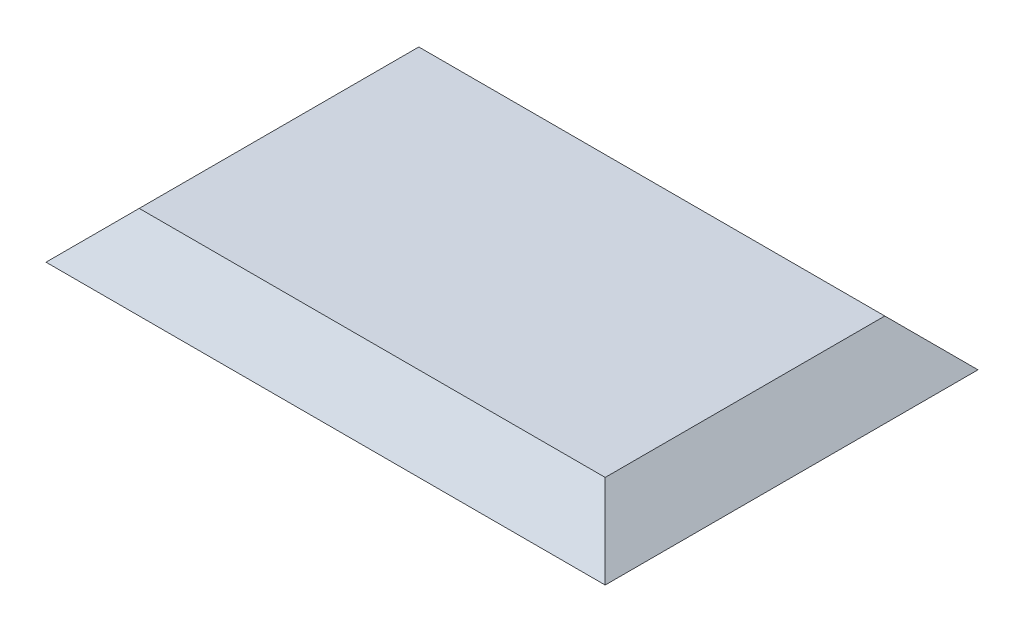
SolidWorks part; units mm, degrees
ref_plane "Plan de face" through (0, 0, 0) normal (0, 0, 1) x (1, 0, 0)
ref_plane "Plan de dessus" through (0, 0, 0) normal (0, 1, 0) x (1, 0, 0)
ref_plane "Plan de droite" through (0, 0, 0) normal (1, 0, 0) x (0, 0, -1)
sketch "Esquisse1" plane through (0, 0, 0) normal (0, 1, 0) x (1, 0, 0)
  line L1 (1.8, -1.2) -> (-1.8, -1.2)
  line L2 (1.8, -1.2) -> (1.8, 1.2)
  line L3 (1.8, 1.2) -> (-1.8, 1.2)
  line L4 (-1.8, -1.2) -> (-1.8, 1.2)
  line L5 (1.8, -1.2) -> (-1.8, 1.2) construction
  line L6 (1.8, 1.2) -> (-1.8, -1.2) construction
  point P0 (0, 0)
  dimension "D1" = 3.6
  dimension "D2" = 2.4
extrude "Boss.-Extru.1" add sketch "Esquisse1" along normal blind 0.6
chamfer "Chanfrein1" distance 0.3 angle 45 8 edges at (0, 0, 1.2) (1.8, 0, 0) (0, 0, -1.2) (-1.8, 0, 0) (0, 0.6, -1.2) (1.8, 0.6, 0) (0, 0.6, 1.2) (-1.8, 0.6, 0)
